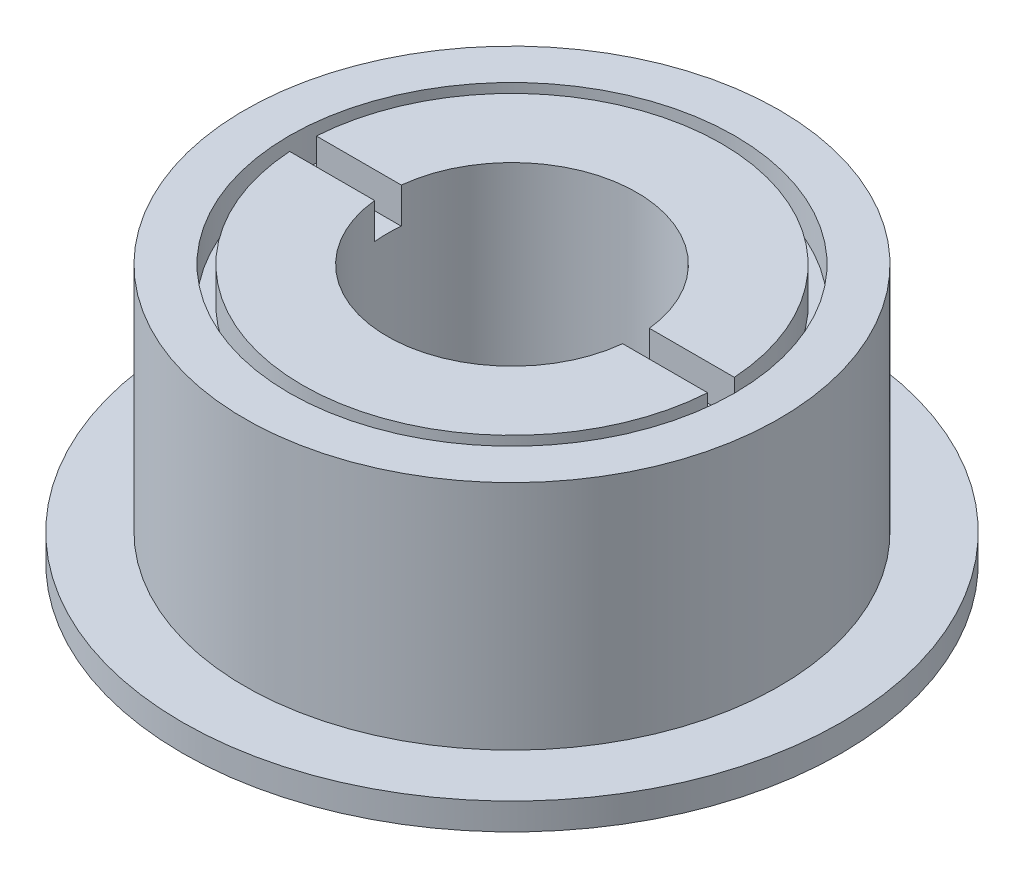
SolidWorks part; units mm, degrees
note: The reader was unsure of these and kept them because the rebuilt part matched: shared geometry of "Sketch1<3>".
ref_plane "Front Plane" through (0, 0, 0) normal (0, 0, 1) x (1, 0, 0)
ref_plane "Top Plane" through (0, 0, 0) normal (0, 1, 0) x (1, 0, 0)
ref_plane "Right Plane" through (0, 0, 0) normal (1, 0, 0) x (0, 0, -1)
sketch "Sketch1" plane through (0, 0, 0) normal (0, 1, 0) x (1, 0, 0)
  circle A0 centre (0, 0) radius 37
  circle A1 centre (0, 0) radius 30
  circle A2 centre (0, 0) radius 14
  dimension "D1" = 74
  dimension "D2" = 60
  dimension "D3" = 28
extrude "Boss-Extrude1" add sketch "Sketch1" along normal blind 3 contours A0
extrude "Boss-Extrude2" add sketch "Sketch1<3>" along normal blind 29 contours A1 A2
sketch "Sketch1<3>" plane through (0, 0, 0) normal (0, 1, 0) x (1, 0, 0) same geometry as "Sketch1"
sketch "Sketch2" plane through (0, 29, 0) normal (0, 1, 0) x (1, 0, 0)
  line L1 (-35, -1.5) -> (35, -1.5)
  line L2 (-35, -1.5) -> (-35, 1.5)
  line L3 (-35, 1.5) -> (35, 1.5)
  line L4 (35, -1.5) -> (35, 1.5)
  line L5 (-35, -1.5) -> (35, 1.5) construction
  line L6 (-35, 1.5) -> (35, -1.5) construction
  circle A0 centre (0, 0) radius 25
  circle A1 centre (0, 0) radius 23.5
  circle M3 centre (0, 0) radius 14
  dimension "D1" = 50
  dimension "D2" = 47
  dimension "D3" = 3
  dimension "D4" = 70
extrude "Cut-Extrude1" cut sketch "Sketch2" against normal blind 4 contours A0 A1 | A1 L3 A0 | A1 L3 A0 L1 | L3 A1 L1 M3 | L1 A1 L3 M3 | A1 L1 A0 L3
sketch "Sketch3" plane through (0, 0, 0) normal (0, -1, 0) x (1, 0, 0)
  circle A0 centre (0, 0) radius 4
  circle A1 centre (-8, 0) radius 2
  circle A2 centre (0, 8) radius 2
  circle A3 centre (8, 0) radius 2
  circle A4 centre (0, -8) radius 2
  point P14 (0, 0)
  dimension "D1" = 8
  dimension "D3" = 4
  dimension "D2" = 8
  dimension "D4" = 4
extrude "Cut-Extrude2" cut sketch "Sketch3" against normal blind 4
